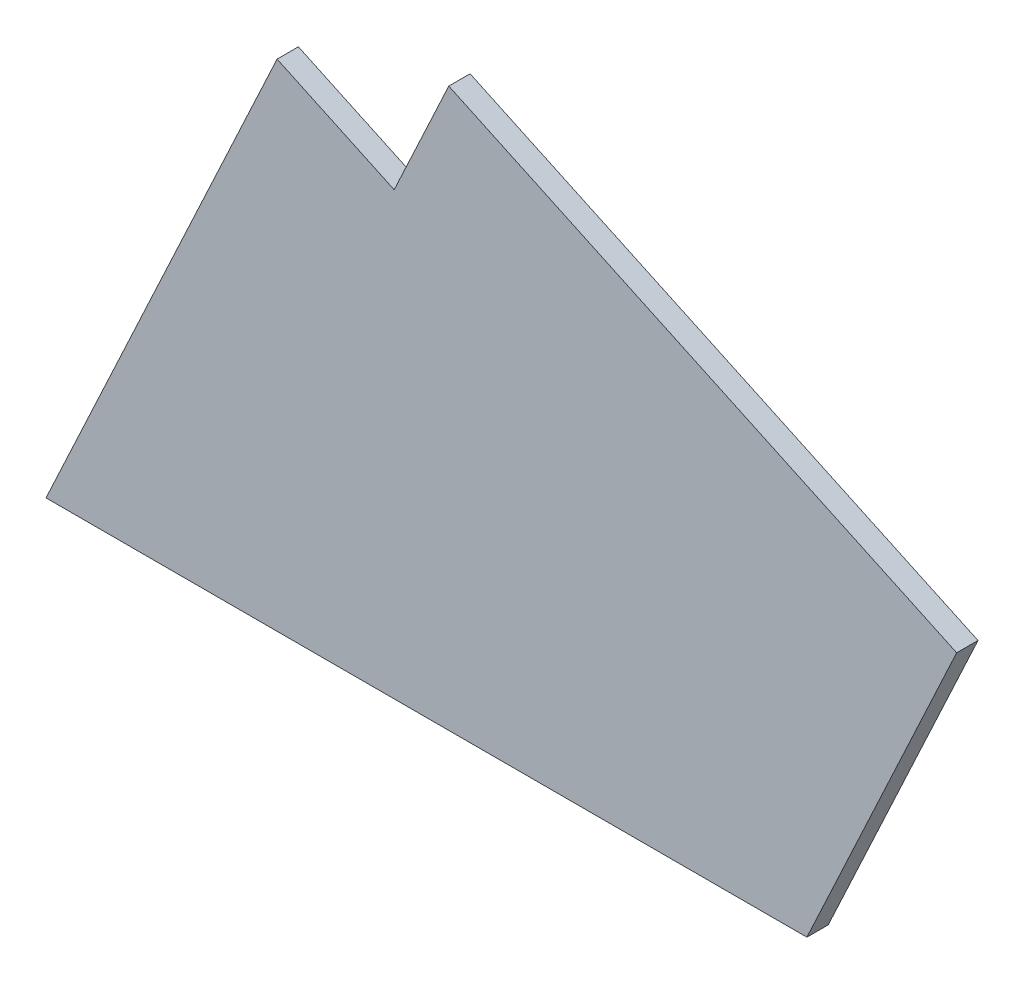
SolidWorks part; units mm, degrees
material "Balsa"
ref_plane "Front Plane" through (0, 0, 0) normal (0, 0, 1) x (1, 0, 0)
ref_plane "Top Plane" through (0, 0, 0) normal (0, 1, 0) x (1, 0, 0)
ref_plane "Right Plane" through (0, 0, 0) normal (1, 0, 0) x (0, 0, -1)
sketch "Sketch1" plane through (0, 0, 396.7) normal (0, 0, 1) x (1, 0, 0)
  line L0 (-321.5462, 12.6346) -> (-203.7639, 12.6346)
  line L2 (-321.5462, 12.6346) -> (-285.7774, 89.341)
  line L3 (-285.7774, 89.341) -> (-267.6513, 80.8887)
  line L4 (-267.6513, 80.8887) -> (-259.1989, 99.0148)
  line L5 (-259.1989, 99.0148) -> (-180.5794, 62.354)
  line L6 (-180.5794, 62.354) -> (-203.7639, 12.6346)
  line L7 (-176.6689, 0) -> (-153.4844, 49.7193) construction
  line L8 (-255.5737, 97.3243) -> (63.4467, -51.4373) construction
  line L10 (-327.4362, 0.0035) -> (-285.7774, 89.341) construction
  line L11 (-285.7774, 89.341) -> (-267.6513, 80.8887) construction
  line L12 (-267.6513, 80.8887) -> (-259.1989, 99.0148) construction
  point P10 (-203.7639, 12.6346)
  point P11 (-321.5462, 12.6346)
extrude "Boss-Extrude1" add sketch "Sketch1" against normal blind 3.3
